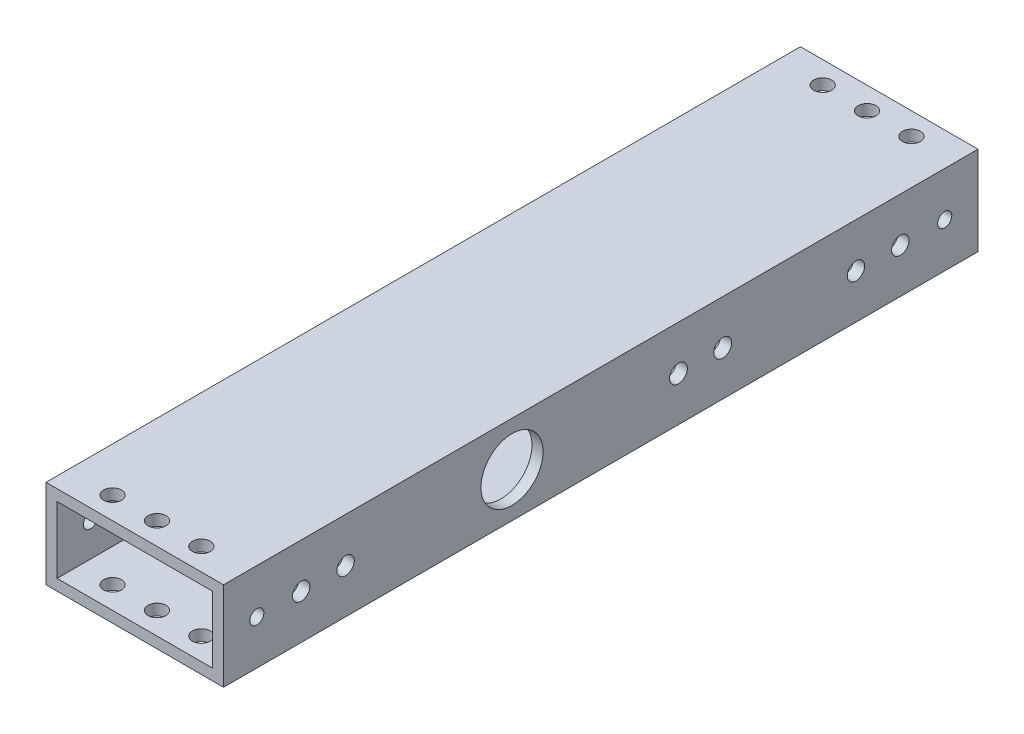
SolidWorks part; units mm, degrees
material "6061-T6 (SS)"
ref_plane "Front Plane" through (0, 0, 0) normal (0, 0, 1) x (1, 0, 0)
ref_plane "Top Plane" through (0, 0, 0) normal (0, 1, 0) x (1, 0, 0)
ref_plane "Right Plane" through (0, 0, 0) normal (1, 0, 0) x (0, 0, -1)
sketch "Sketch1" plane through (0, 0, 0) normal (0, 0, 1) x (1, 0, 0)
  line L0 (-22.225, 9.525) -> (22.225, 9.525)
  line L1 (-25.4, -12.7) -> (25.4, -12.7)
  line L2 (-25.4, -12.7) -> (-25.4, 12.7)
  line L3 (-25.4, 12.7) -> (25.4, 12.7)
  line L4 (25.4, -12.7) -> (25.4, 12.7)
  line L5 (-25.4, -12.7) -> (25.4, 12.7) construction
  line L6 (-25.4, 12.7) -> (25.4, -12.7) construction
  line L7 (22.225, -9.525) -> (22.225, 9.525)
  line L8 (-22.225, -9.525) -> (22.225, -9.525)
  line L9 (-22.225, -9.525) -> (-22.225, 9.525)
  point P0 (0, 0)
  dimension "D1" = 50.8
  dimension "D2" = 25.4
  dimension "D3" = 3.175
extrude "Boss-Extrude1" add sketch "Sketch1" along normal mid plane 215.9
sketch "Sketch2" plane through (25.4, 0, 0) normal (1, 0, 0) x (0, 0, -1)
  line L0 (-107.95, -12.7) -> (-107.95, 12.7) construction
  line L1 (0, 12.7) -> (0, -12.7) construction
  line L2 (-107.95, 12.7) -> (107.95, 12.7) construction
  line L3 (-107.95, -12.7) -> (107.95, -12.7) construction
  circle A0 centre (-98.425, 0) radius 2.0193
  circle A1 centre (98.425, 0) radius 2.0193
  circle A2 centre (-85.725, 0) radius 2.4892
  circle A3 centre (-73.025, 0) radius 2.4892
  circle A4 centre (73.025, 0) radius 2.4892
  circle A5 centre (85.725, 0) radius 2.4892
  dimension "D2" = 4.0386
  dimension "D5" = 4.9784
  dimension "D1" = 9.525
  dimension "D3" = 12.7
  dimension "D4" = 12.7
extrude "Cut-Extrude1" cut sketch "Sketch2" against normal through all
sketch "Sketch3" plane through (0, 12.7, 0) normal (0, 1, 0) x (1, 0, 0)
  line L0 (-25.4, 0) -> (25.4, 0) construction
  line L1 (-25.4, -107.95) -> (-25.4, 107.95) construction
  line L2 (25.4, -107.95) -> (25.4, 107.95) construction
  line L3 (25.4, -107.95) -> (-25.4, -107.95) construction
  circle A0 centre (-12.7, -101.6) radius 2.5527
  circle A1 centre (0, -101.6) radius 2.5527
  circle A2 centre (12.7, -101.6) radius 2.5527
  circle A3 centre (12.7, 101.6) radius 2.5527
  circle A4 centre (0, 101.6) radius 2.5527
  circle A5 centre (-12.7, 101.6) radius 2.5527
  dimension "D1" = 5.1054
  dimension "D2" = 12.7
  dimension "D3" = 12.7
  dimension "D4" = 6.35
extrude "Cut-Extrude2" cut sketch "Sketch3" against normal through all
sketch "Sketch4" plane through (25.4, 0, 0) normal (1, 0, 0) x (0, 0, -1)
  line L0 (-25.4, 0) -> (-45.1908, 0) construction
  line L1 (-16.51, 0) -> (-34.29, 0) construction
  line L8 (-25.4, 0) -> (34.925, 0) construction
  line L9 (0, 12.7) -> (0, -12.7) construction
  line L10 (-107.95, 12.7) -> (107.95, 12.7) construction
  line L11 (-107.95, -12.7) -> (107.95, -12.7) construction
  circle A0 centre (-25.4, 0) radius 8.89
  circle A9 centre (34.925, 0) radius 2.5527
  circle A10 centre (22.225, 0) radius 2.5527
  dimension "D2" = 17.78
  dimension "D3" = 25.4
  dimension "D1" = 60.325
  dimension "D4" = 5.1054
  dimension "D6" = 47.625
extrude "Cut-Extrude3" cut sketch "Sketch4" against normal through all contours A0 | A9 | A10
sketch "Sketch5" plane through (0, -12.7, 0) normal (0, -1, 0) x (1, 0, 0)
  line L0 (-25.4, 107.95) -> (-25.4, -107.95) construction
  line L1 (-25.4, 107.95) -> (25.4, 107.95) construction
  line L4 (25.4, 25.4) -> (-25.4, 25.4) construction
  line L5 (25.4, 107.95) -> (25.4, -107.95) construction
  circle A0 centre (-3.81, 69.85) radius 2.4892
  circle A1 centre (-16.51, 69.85) radius 2.4892
  circle A2 centre (-16.51, 57.15) radius 2.4892
  circle A3 centre (-3.81, 57.15) radius 2.4892
  circle A8 centre (-3.81, -6.35) radius 2.4892
  circle A9 centre (-16.51, -6.35) radius 2.4892
  circle A10 centre (-16.51, -19.05) radius 2.4892
  circle A11 centre (-3.81, -19.05) radius 2.4892
  dimension "D3" = 4.9784
  dimension "D4" = 8.89
  dimension "D7" = 12.7
  dimension "D12" = 82.55
  dimension "D5" = 31.75
  dimension "D6" = 12.7
  dimension "D1" = 2
  dimension "D2" = 2
extrude "Cut-Extrude4" cut sketch "Sketch5" against normal up to next
